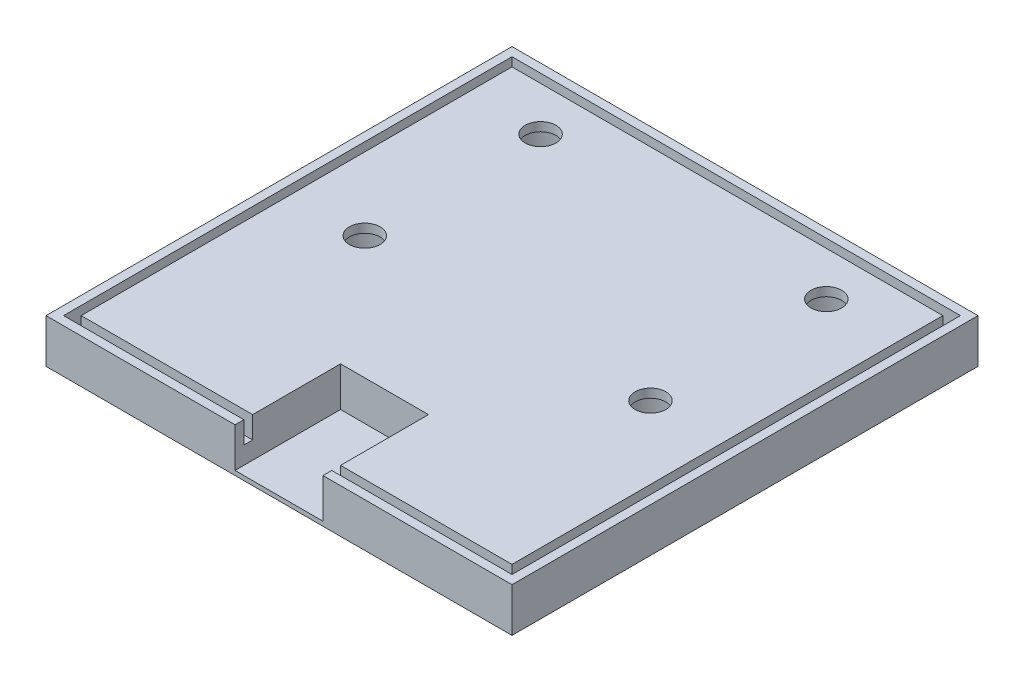
SolidWorks part; units mm, degrees
ref_plane "Front Plane" through (0, 0, 0) normal (0, 0, 1) x (1, 0, 0)
ref_plane "Top Plane" through (0, 0, 0) normal (0, 1, 0) x (1, 0, 0)
ref_plane "Right Plane" through (0, 0, 0) normal (1, 0, 0) x (0, 0, -1)
sketch "Sketch1" plane through (0, 0, 0) normal (0, 1, 0) x (1, 0, 0)
  line L0 (0, 0) -> (102, 0)
  line L1 (102, 0) -> (102, -102)
  line L2 (102, -102) -> (0, -102)
  line L3 (0, -102) -> (0, 0)
  line L4 (2, -2) -> (100, -2)
  line L5 (100, -2) -> (100, -100)
  line L6 (100, -100) -> (2, -100)
  line L7 (2, -100) -> (2, -2)
  line L8 (-2, 2) -> (104, 2)
  line L9 (104, 2) -> (104, -104)
  line L10 (104, -104) -> (-2, -104)
  line L11 (-2, -104) -> (-2, 2)
  line L12 (51, -100) -> (51, -80)
  line L13 (51, -80) -> (61, -80)
  line L14 (61, -80) -> (61, -100)
  line L15 (51, -80) -> (41, -80)
  line L16 (41, -80) -> (41, -100)
  line L17 (41, -102) -> (41, -104)
  line L18 (61, -102) -> (61, -104)
  line L19 (61, -104) -> (41, -104)
  line L20 (41, -102) -> (61, -102)
  line L21 (41, -102) -> (41, -100)
  line L22 (61, -102) -> (61, -100)
  line L23 (41, -100) -> (61, -100)
  line L24 (61, -102) -> (41, -102)
  circle A0 centre (18.5, -12) radius 3.5
  circle A1 centre (83.5, -12) radius 3.5
  circle A2 centre (18.5, -52) radius 3.5
  circle A3 centre (83.5, -52) radius 3.5
  circle A4 centre (18.5, -12) radius 8.5
  circle A5 centre (83.5, -12) radius 8.5
  circle A6 centre (18.5, -52) radius 8.5
  circle A7 centre (83.5, -52) radius 8.5
  point P31 (41, -103)
  dimension "D5" = 7
  dimension "D6" = 7
  dimension "D11" = 7
  dimension "D12" = 7
  dimension "D1" = 102
  dimension "D2" = 102
  dimension "D7" = 10
  dimension "D8" = 10
  dimension "D9" = 16.5
  dimension "D10" = 16.5
  dimension "D13" = 40
  dimension "D14" = 40
  dimension "D15" = 16.5
  dimension "D16" = 16.5
  dimension "D17" = 10
  dimension "D18" = 10
  dimension "D19" = 20
  dimension "D20" = 3
  dimension "D3" = 2
  dimension "D4" = 2
  dimension "D21" = 5
  dimension "D22" = 5
  dimension "D23" = 5
  dimension "D24" = 5
extrude "Boss-Extrude1" add sketch "Sketch1" along normal blind 10 contours L2 L18 L10 L9 L8 L11 L17 L3 L0 L1 | L16 L15 L13 L14 L6 L5 L4 L7 A3 A2 A1 A0 | A4 | A0 | A6 | A2 | A7 | A3 | A5 | A1 region at (-1.4991, 0, 51) region at (51, 0, 51.1989) region at (10.2404, 0, 12) region at (75.2404, 0, 12) region at (10.2404, 0, 52) region at (75.2404, 0, 52)
extrude "Boss-Extrude2" add sketch "Sketch1<5>" along normal blind 5 contours L22 L2 L1 L0 L3 L21 L6 L7 L4 L5 region at (51, 0, 1.4425)
sketch "Sketch1<5>" plane through (0, 0, 0) normal (0, 1, 0) x (1, 0, 0) same geometry as "Sketch1"
extrude "Boss-Extrude3" add sketch "Sketch1<6>" along normal blind 1 contours L15 L16 L6 L12 | L14 L13 L12 L6 | L2 L22 L6 L21 | L18 L2 L17 L10 region at (51, 0, 101) region at (51, 0, 103) region at (46, 0, 90) region at (56, 0, 90)
sketch "Sketch1<6>" plane through (0, 0, 0) normal (0, 1, 0) x (1, 0, 0) same geometry as "Sketch1"
extrude "Cut-Extrude1" cut sketch "Sketch1<7>" along normal blind 8 contours A6 A2 | A7 A3 | A5 A1 | A4 A0 region at (10.2404, 0, 12) region at (75.2404, 0, 12) region at (10.2404, 0, 52) region at (75.2404, 0, 52)
sketch "Sketch1<7>" plane through (0, 0, 0) normal (0, 1, 0) x (1, 0, 0) same geometry as "Sketch1"
sketch "Sketch2" plane through (0, 0, 0) normal (0, -1, 0) x (1, 0, 0)
  line L2 (98, 98) -> (4, 98)
  line L4 (104, 104) -> (-2, 104) construction
  line L5 (51, 98) -> (63, 98)
  line L6 (63, 98) -> (63, 76)
  line L7 (63, 76) -> (51, 76)
  line L8 (51, 76) -> (39, 76)
  line L9 (39, 76) -> (39, 98)
  line L10 (39, 98) -> (51, 98)
  line L11 (-2, -2) -> (104, -2) construction
  line L13 (-2, 104) -> (-2, -2) construction
  line L15 (4, 98) -> (4, 1)
  line L18 (98, 1) -> (98, 98)
  line L19 (104, -2) -> (104, 104) construction
  line L20 (98, 4.5745) -> (90.627, 4.5745)
  line L21 (90.627, 4.5745) -> (76.373, 4.5745)
  line L22 (76.373, 4.5745) -> (26.4542, 4.5745)
  line L23 (26.4542, 4.5745) -> (10.5458, 4.5745)
  line L24 (10.5458, 4.5745) -> (4, 4.5745)
  circle A0 centre (83.5, 12) radius 10.2923
  circle A1 centre (18.5, 12) radius 10.8815
  circle A2 centre (83.5, 52) radius 10.1949
  circle A3 centre (18.5, 52) radius 10.2613
  dimension "D1" = 6
  dimension "D2" = 6
  dimension "D3" = 12
  dimension "D4" = 12
  dimension "D5" = 22
  dimension "D6" = 12
  dimension "D7" = 6
  dimension "D8" = 6.5745
extrude "Cut-Extrude4" cut sketch "Sketch2" against normal blind 8 contours A1 L22 A0 L20 L18 L2 L6 L7 L8 L9 L15 L24 A3 A2 region at (51.1568, 0, 52.0332)
